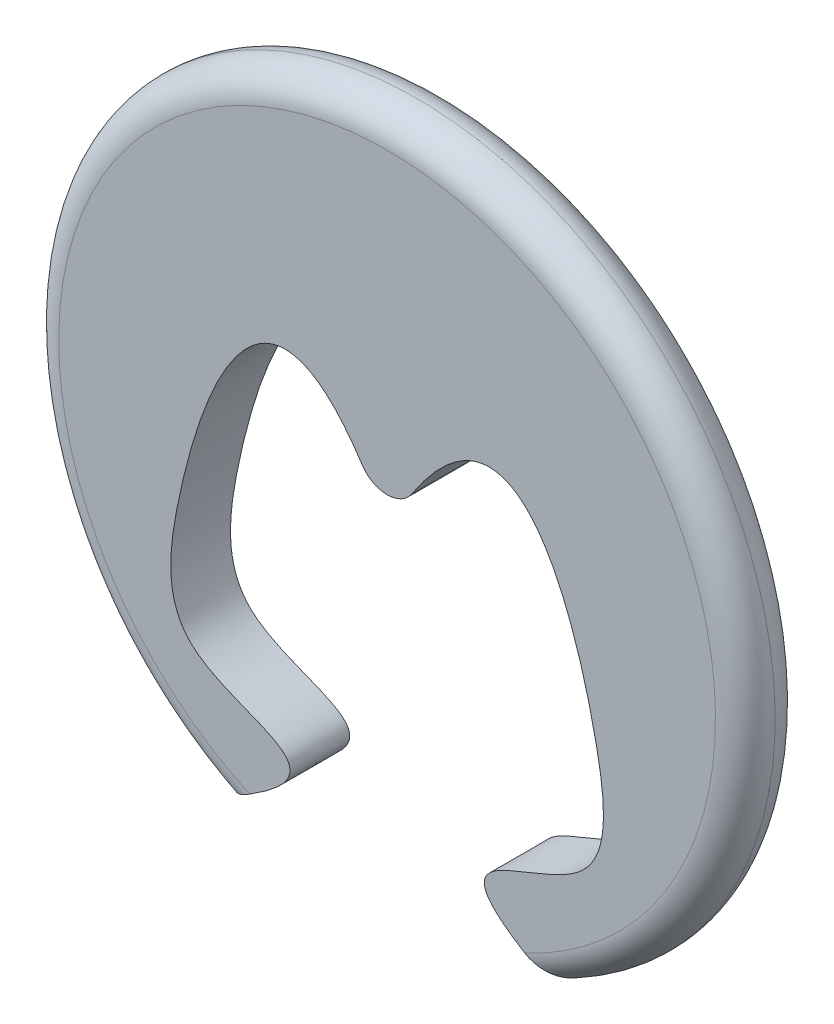
SolidWorks part; units mm, degrees
ref_plane "Alzado" through (0, 0, 0) normal (0, 0, 1) x (1, 0, 0)
ref_plane "Planta" through (0, 0, 0) normal (0, 1, 0) x (1, 0, 0)
ref_plane "Vista lateral" through (0, 0, 0) normal (1, 0, 0) x (0, 0, -1)
sketch "Croquis1" plane through (0, 0, 0) normal (0, 0, 1) x (1, 0, 0)
  arc A0 (5.6558, -10.5836) -> (-5.6558, -10.5836) centre (0, 0) ccw
  spline S0 degree 3 poles (-5.6558, -10.5836) (-0.4745, -7.8338) (-7.7532, -8.2224) (-6.8097, 0.322) (-3.6598, 7.1174) (0, 0) knots 0 0 0 0 0.294178 0.466965 1 1 1 1
  spline S1 degree 3 poles (5.6558, -10.5836) (0.4745, -7.8338) (7.7532, -8.2224) (6.8097, 0.322) (3.6598, 7.1174) (0, 0) knots 0 0 0 0 0.294178 0.466965 1 1 1 1
  dimension "D1" = 12
extrude "Saliente-Extruir1" add sketch "Croquis1" along normal blind 2
fillet "Redondeo1" radius 1 1 edges at (0, 0, 1)
fillet "Redondeo2" radius 1 2 edges at (0, 12, 2) (0, 12, 0)
